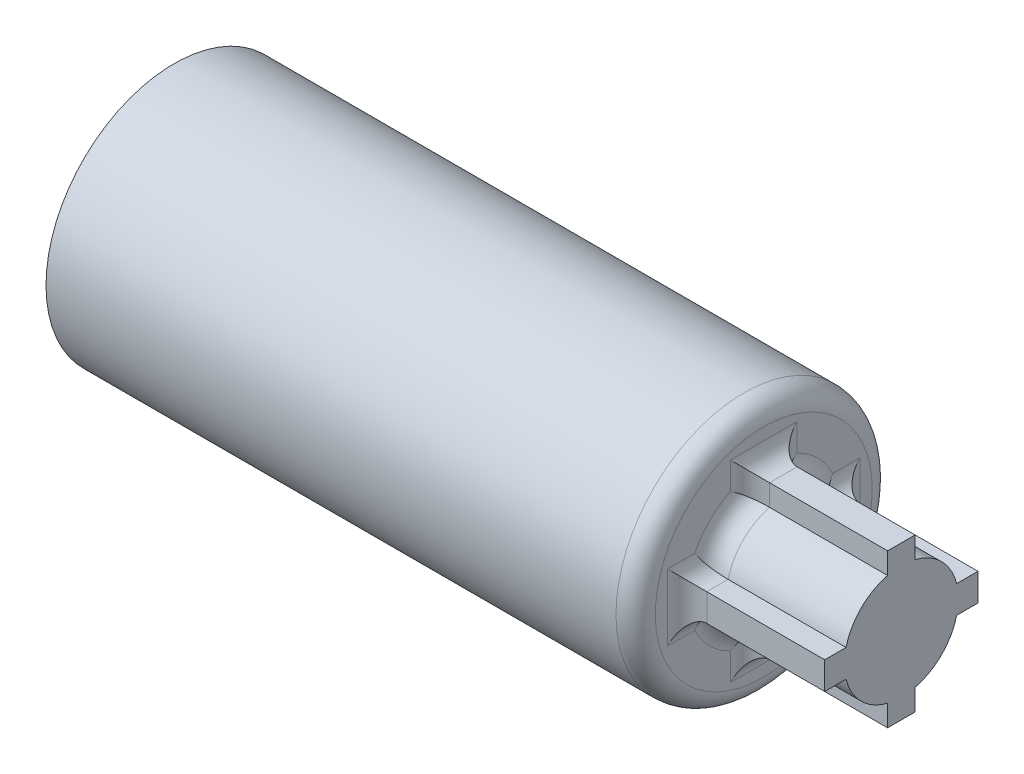
SolidWorks part; units mm, degrees
ref_plane "Front Plane" through (0, 0, 0) normal (0, 0, 1) x (1, 0, 0)
ref_plane "Top Plane" through (0, 0, 0) normal (0, 1, 0) x (1, 0, 0)
ref_plane "Right Plane" through (0, 0, 0) normal (1, 0, 0) x (0, 0, -1)
sketch "Sketch1" plane through (9.0729, 0, 0) normal (-1, 0, 0) x (0, 0, 1)
  line L0 (-22.5649, -14.994) -> (-21.5649, -14.994)
  line L1 (-24.1649, -19.194) -> (-19.9649, -19.194) construction
  line L2 (-24.1649, -19.194) -> (-24.1649, -14.994) construction
  line L3 (-24.1649, -14.994) -> (-19.9649, -14.994) construction
  line L4 (-19.9649, -19.194) -> (-19.9649, -14.994) construction
  line L5 (-24.1649, -19.194) -> (-19.9649, -14.994) construction
  line L6 (-24.1649, -14.994) -> (-19.9649, -19.194) construction
  line L7 (-21.5649, -14.994) -> (-21.5649, -15.5742)
  line L8 (-22.5649, -14.994) -> (-22.5649, -15.5742)
  line L9 (-19.9649, -16.594) -> (-20.545, -16.594)
  line L10 (-19.9649, -16.594) -> (-19.9649, -17.594)
  line L11 (-19.9649, -17.594) -> (-20.545, -17.594)
  line L12 (-21.5649, -19.194) -> (-21.5649, -18.6139)
  line L13 (-21.5649, -19.194) -> (-22.5649, -19.194)
  line L14 (-22.5649, -19.194) -> (-22.5649, -18.6139)
  line L15 (-24.1649, -17.594) -> (-23.5848, -17.594)
  line L16 (-24.1649, -17.594) -> (-24.1649, -16.594)
  line L17 (-24.1649, -16.594) -> (-23.5848, -16.594)
  line L18 (-24.0149, -16.744) -> (-23.472, -16.744)
  line L19 (-22.4149, -15.144) -> (-22.4149, -15.6869)
  line L20 (-22.4149, -15.144) -> (-21.7149, -15.144)
  line L21 (-21.7149, -15.144) -> (-21.7149, -15.6869)
  line L22 (-20.1149, -16.744) -> (-20.6578, -16.744)
  line L23 (-20.1149, -16.744) -> (-20.1149, -17.444)
  line L24 (-20.1149, -17.444) -> (-20.6578, -17.444)
  line L25 (-21.7149, -19.044) -> (-21.7149, -18.5012)
  line L26 (-21.7149, -19.044) -> (-22.4149, -19.044)
  line L27 (-22.4149, -19.044) -> (-22.4149, -18.5012)
  line L28 (-24.0149, -17.444) -> (-23.472, -17.444)
  line L29 (-24.0149, -17.444) -> (-24.0149, -16.744)
  line L30 (-20.9989, -49.3667) -> (-16.1659, 14.4506) construction
  line L31 (-20.9989, -49.3667) -> (-16.1659, 14.4506) construction
  line L32 (-23.7116, -18.9751) -> (-20.7202, -19.2016) construction
  line L33 (-23.7521, -19.0723) -> (-20.6949, -19.3038)
  circle A0 centre (-22.0649, -17.094) radius 1.6 construction
  arc A1 (-23.5848, -17.594) -> (-22.5649, -18.6139) centre (-22.0649, -17.094) ccw construction
  arc A2 (-23.5848, -17.594) -> (-22.5649, -18.6139) centre (-22.0649, -17.094) ccw
  arc A3 (-22.5649, -15.5742) -> (-23.5848, -16.594) centre (-22.0649, -17.094) ccw construction
  arc A4 (-22.5649, -15.5742) -> (-23.5848, -16.594) centre (-22.0649, -17.094) ccw
  arc A5 (-20.545, -16.594) -> (-21.5649, -15.5742) centre (-22.0649, -17.094) ccw construction
  arc A6 (-20.545, -16.594) -> (-21.5649, -15.5742) centre (-22.0649, -17.094) ccw
  arc A7 (-21.5649, -18.6139) -> (-20.545, -17.594) centre (-22.0649, -17.094) ccw construction
  arc A8 (-21.5649, -18.6139) -> (-20.545, -17.594) centre (-22.0649, -17.094) ccw
  arc A9 (-22.4149, -15.6869) -> (-23.472, -16.744) centre (-22.0649, -17.094) ccw
  arc A10 (-20.6578, -16.744) -> (-21.7149, -15.6869) centre (-22.0649, -17.094) ccw
  arc A11 (-21.7149, -18.5012) -> (-20.6578, -17.444) centre (-22.0649, -17.094) ccw
  arc A12 (-23.472, -17.444) -> (-22.4149, -18.5012) centre (-22.0649, -17.094) ccw
  arc A13 (-21.8761, -14.6012) -> (-23.7116, -18.9751) centre (-22.0649, -17.094) ccw construction
  arc A14 (-20.7202, -19.2016) -> (-21.8761, -14.6012) centre (-22.0649, -17.094) ccw construction
  arc A15 (-21.8761, -14.6012) -> (-23.7116, -18.9751) centre (-22.0649, -17.094) ccw construction
  arc A16 (-20.7202, -19.2016) -> (-21.8761, -14.6012) centre (-22.0649, -17.094) ccw construction
  arc A17 (-20.6949, -19.3038) -> (-21.8685, -14.5015) centre (-22.0649, -17.094) ccw
  arc A18 (-21.8685, -14.5015) -> (-23.7521, -19.0723) centre (-22.0649, -17.094) ccw
  circle A19 centre (-22.0649, -17.094) radius 3.2593
  point P9 (-22.0649, -14.994)
  point P12 (-22.0649, -14.994)
  point P55 (-18.8056, -17.094)
  circle M24 centre (-22.0649, -17.094) radius 1.6
  dimension "D3" = 4
  dimension "D4" = 0.15
  dimension "D1" = 4.2
  dimension "D2" = 1
  dimension "D5" = 0.1
  dimension "D6" = 0.25
extrude "Boss-Extrude1" add sketch "Sketch1" against normal blind 3.5 contours L28 A12 L27 L25 A11 L24 L22 A10 L21 L19 A9 L18 M24 | L29 L28 L18 M24 | L21 L20 L19 M24 | L24 L23 L22 M24 | L27 L26 L25 M24 region at (9.0729, -17.094, -22.0649) region at (9.0729, -15.3257, -22.0649) region at (9.0729, -17.094, -23.8333) region at (9.0729, -17.094, -20.2965) region at (9.0729, -18.8624, -22.0649)
extrude "Boss-Extrude2" add sketch "Sketch1<3>" along normal blind 1 contours A19
sketch "Sketch1<3>" plane through (9.0729, 0, 0) normal (-1, 0, 0) x (0, 0, 1) same geometry as "Sketch1"
extrude "Boss-Extrude3" add sketch "Sketch1<4>" along normal blind 15 contours A19 A18 A17 L33 L13 | L33 L14 L13 region at (9.0729, -19.1834, -22.4247) region at (9.0729, -17.094, -25.232)
sketch "Sketch1<4>" plane through (9.0729, 0, 0) normal (-1, 0, 0) x (0, 0, 1) same geometry as "Sketch1"
fillet "Fillet1" radius 0.5 17 edges at (9.0729, -20.3533, -22.0649) (9.0729, -16.744, -23.7435) (9.0729, -16.0687, -23.0902) (9.0729, -15.4155, -22.4149) (9.0729, -15.144, -22.0649) (9.0729, -15.4155, -21.7149) (9.0729, -16.0687, -21.0396) (9.0729, -16.744, -20.3863) (9.0729, -17.094, -20.1149) (9.0729, -17.444, -20.3863) (9.0729, -18.1193, -21.0396) (9.0729, -18.7726, -21.7149) (9.0729, -19.044, -22.0649) (9.0729, -18.7726, -22.4149) (9.0729, -18.1193, -23.0902) (9.0729, -17.444, -23.7435) (9.0729, -17.094, -24.0149)
